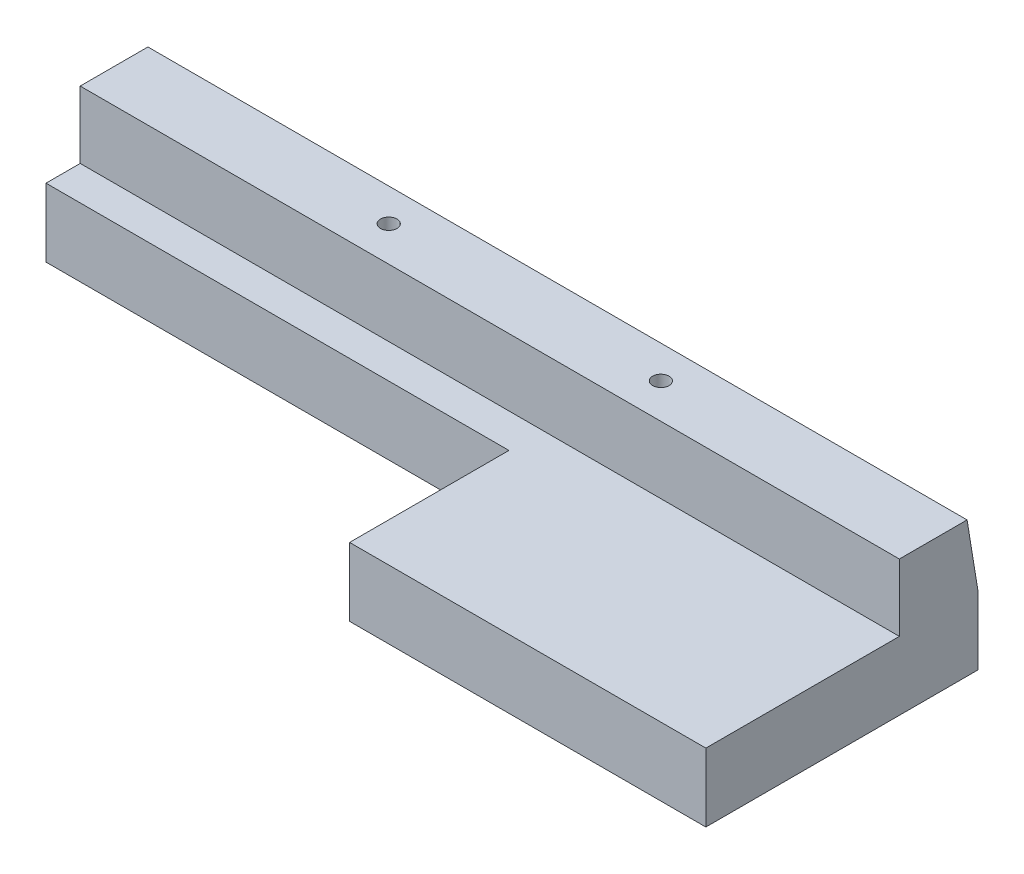
SolidWorks part; units mm, degrees
ref_plane "Płaszczyzna przednia" through (0, 0, 0) normal (0, 0, 1) x (1, 0, 0)
ref_plane "Płaszczyzna górna" through (0, 0, 0) normal (0, 1, 0) x (1, 0, 0)
ref_plane "Płaszczyzna prawa" through (0, 0, 0) normal (1, 0, 0) x (0, 0, -1)
sketch "Szkic1" plane through (0, 0, 0) normal (0, 0, 1) x (1, 0, 0)
  line L1 (-58.3066, 32.0248) -> (61.4934, 32.0248)
  line L2 (-58.3066, 32.0248) -> (-58.3066, 22.0248)
  line L3 (-58.3066, 22.0248) -> (61.4934, 22.0248)
  line L4 (61.4934, 32.0248) -> (61.4934, 22.0248)
  dimension "D1" = 119.8
  dimension "D2" = 10
extrude "Dodanie-wyciągnięcie2" add sketch "Szkic1" along normal blind 38.3 contours L2 L3 L4 L1
sketch "Szkic21" plane through (0, 32.0248, 0) normal (0, 1, 0) x (1, 0, 0)
  line L0 (61.4934, -38.3) -> (61.4934, 0) construction
  line L1 (-58.3066, 0) -> (61.4934, 0)
  line L2 (-58.3066, 0) -> (-58.3066, -10)
  line L3 (-58.3066, -10) -> (61.4934, -10)
  line L4 (61.4934, 0) -> (61.4934, -10)
extrude "Dodanie-wyciągnięcie3" add sketch "Szkic21" along normal blind 9.8
sketch "Szkic22" plane through (0, 22.0248, 0) normal (0, -1, 0) x (1, 0, 0)
  line L0 (-58.3066, 4.88) -> (-18.3066, 4.88) construction
  line L1 (-58.3066, 38.3) -> (-58.3066, 0) construction
  line L2 (-18.3066, 4.88) -> (21.4934, 4.88) construction
  line L3 (21.4934, 4.88) -> (61.4934, 4.88) construction
  line L4 (61.4934, 38.3) -> (61.4934, 0) construction
  line L5 (1.9729, 4.88) -> (1.9729, 0) construction
  line L6 (-58.3066, 0) -> (61.4934, 0) construction
hole_wizard "Pogłębienie walcowe pod M2 wkręt do części metalowych z łbem stożkowym ściętym2" positions "Szkic23" profile "Szkic24" counterbore size "M2" standard "Ansi Metric" end condition through all
sketch "Szkic23" plane through (0, 22.0248, 0) normal (0, -1, 0) x (-1, 0, 0)
  point P0 (-21.4934, -4.88)
  point P3 (18.3066, -4.88)
sketch "Szkic24" plane through (21.4934, 22.0248, 4.88) normal (1, 0, 0) x (0, 0, -1)
  line L0 (0, 0) -> (0, 19.8)
  line L1 (0, 19.8) -> (1.2, 19.8)
  line L3 (1.2, 19.8) -> (1.2, 1.6)
  line L4 (1.2, 1.6) -> (2.5, 1.6)
  line L5 (2.5, 1.6) -> (2.5, 0)
  line L7 (2.5, 0) -> (0, 0)
  line L11 (0, -6.35) -> (0, 107.95) construction
  dimension "Średnica otworu na wylot" = 2.4
  dimension "Głębokość otworu na wylot" = 19.8
  dimension "Średnica pogłębienia walcowego" = 5
  dimension "Głębokość pogłębienia walcowego" = 1.6
sketch "Szkic28" plane through (0, 22.0248, 0) normal (0, -1, 0) x (1, 0, 0)
  line L0 (36.4934, 0) -> (36.4934, 23.3) construction
  line L1 (-58.3066, 0) -> (61.4934, 0) construction
  line L2 (36.4934, 23.3) -> (61.4934, 23.3) construction
  line L3 (61.4934, 38.3) -> (61.4934, 0) construction
  line L4 (-58.3066, 38.3) -> (61.4934, 38.3) construction
  circle A0 centre (36.4934, 23.3) radius 11.1
  dimension "D1" = 15
extrude "Wytnij-wyciągnięcie1" cut sketch "Szkic28" against normal blind 7.2
sketch "Szkic31" plane through (61.4934, 0, 0) normal (1, 0, 0) x (0, 0, -1)
  line L0 (-10, 32.0248) -> (-10, 71.9248)
  line L2 (0, 41.2325) -> (0, 32.0248)
  line L6 (0, 41.8248) -> (0, 22.0248) construction
  line L8 (0, 32.0248) -> (1.5, 32.0248)
  line L10 (-10, 32.0248) -> (1.5, 32.0248)
  line L12 (-10, 71.9248) -> (-5, 71.9248)
  line L13 (-5, 71.9248) -> (1.5, 32.0248)
  line L14 (-0.4105, 43.7521) -> (0.2752, 39.543)
  line L15 (0.2752, 39.543) -> (3.3905, 40.0505)
  line L16 (3.3905, 40.0505) -> (-0.4105, 43.7521)
  line M5 (0, 22.0248) -> (0, 41.8248)
  line M6 (0, 41.8248) -> (-10, 41.8248)
extrude "Wytnij-wyciągnięcie4" cut sketch "Szkic31" against normal blind 124.8 contours L13 M6 M5 region at (61.4934, 41.6274, 0.0322)
extrude "Dodanie-wyciągnięcie5" add sketch "Szkic31<5>" against normal blind 119.8 contours L13 L8 M5 region at (61.4934, 35.0941, -0.5)
sketch "Szkic31<5>" plane through (61.4934, 0, 0) normal (1, 0, 0) x (0, 0, -1) same geometry as "Szkic31"
sketch "Szkic34" plane through (0, 0, 0) normal (0, 0, -1) x (-1, 0, 0)
  line L1 (-61.4934, 32.0248) -> (58.3066, 32.0248)
  line L2 (-61.4934, 32.0248) -> (-61.4934, 22.0248)
  line L3 (-61.4934, 22.0248) -> (58.3066, 22.0248)
  line L4 (58.3066, 32.0248) -> (58.3066, 22.0248)
extrude "Dodanie-wyciągnięcie6" add sketch "Szkic34" along normal blind 1.5
sketch "Szkic37" plane through (0, 32.0248, 0) normal (0, 1, 0) x (1, 0, 0)
  line L1 (61.4934, -38.3) -> (9.3934, -38.3)
  line L2 (61.4934, -38.3) -> (61.4934, -30)
  line L3 (61.4934, -30) -> (9.3934, -30)
  line L4 (9.3934, -38.3) -> (9.3934, -30)
mirror "Lustro2" about plane through (-58.3066, 22.0248, 38.3) normal (0, 1, 0) of bodies 125 144
move or copy body "Obiekt-Przenieś/Kopiuj1" bodies to move or copy 146 copy no translate (0, -36.7663, 0) parameters "D1"=0, "D2"=36.7663, "D3"=0
delete or keep bodies "Obiekt-Usuń/zachowaj 1" type delete bodies bodies 125
sketch "Szkic38" plane through (0, 0, 38.3) normal (0, 0, 1) x (1, 0, 0)
  line L0 (-58.3066, -24.7414) -> (61.4934, -24.7414) construction
  line L1 (-58.3066, -14.7414) -> (9.3934, -14.7414)
  line L2 (-58.3066, -14.7414) -> (-58.3066, -24.7414)
  line L3 (-58.3066, -24.7414) -> (9.3934, -24.7414)
  line L4 (9.3934, -14.7414) -> (9.3934, -24.7414)
extrude "Wytnij-wyciągnięcie5" cut sketch "Szkic38" against normal blind 23.3
mirror "Lustro3" of bodies 148
move or copy body "Obiekt-Przenieś/Kopiuj2" bodies to move or copy 149 copy no translate (0, 52.1563, 0) parameters "D1"=0, "D2"=52.1563, "D3"=0
delete or keep bodies "Obiekt-Usuń/zachowaj 2" type delete bodies bodies 148
